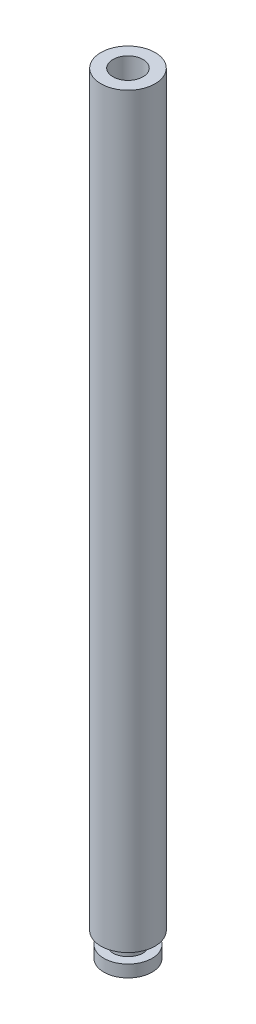
SolidWorks part; units mm, degrees
ref_plane "Front Plane" through (0, 0, 0) normal (0, 0, 1) x (1, 0, 0)
ref_plane "Top Plane" through (0, 0, 0) normal (0, 1, 0) x (1, 0, 0)
ref_plane "Right Plane" through (0, 0, 0) normal (1, 0, 0) x (0, 0, -1)
sketch "Sketch1" plane through (0, 0, 0) normal (0, 1, 0) x (1, 0, 0)
  circle A0 centre (-0.522, 0.5111) radius 1
  circle A1 centre (-0.522, 0.5111) radius 2.25
  dimension "D1" = 2
  dimension "D2" = 4.5
extrude "Boss-Extrude1" add sketch "Sketch1" along normal blind 62 contours A1
extrude "Boss-Extrude2" add sketch "Sketch1<3>" along normal blind 1 contours A0 region at (-0.522, 0, -0.5111)
sketch "Sketch1<3>" plane through (0, 0, 0) normal (0, 1, 0) x (1, 0, 0) same geometry as "Sketch1"
sketch "Sketch5" plane through (0, 0, 0) normal (0, -1, 0) x (1, 0, 0)
  circle A3 centre (-0.522, -0.5111) radius 1.25
  dimension "D1" = 2.5
extrude "Boss-Extrude3" add sketch "Sketch5" along normal blind 1 contours A3
sketch "Sketch6" plane through (0, -1, 0) normal (0, -1, 0) x (1, 0, 0)
  circle A0 centre (-0.522, -0.5111) radius 2
  dimension "D1" = 4
extrude "Boss-Extrude4" add sketch "Sketch6" along normal blind 1
sketch "Sketch8" plane through (0, -2, 0) normal (0, -1, 0) x (-1, 0, 0)
  circle A0 centre (0.522, 0.5111) radius 1.5
  dimension "D1" = 3
sketch "Sketch11" plane through (0, 62, 0) normal (0, 1, 0) x (1, 0, 0)
  text T0 "VIII" font "Century Gothic" height in points 5
sketch "Sketch12" plane through (0, 62, 0) normal (0, 1, 0) x (1, 0, 0)
  circle A0 centre (-0.522, 0.5111) radius 1.25
extrude "Cut-Extrude1" cut sketch "Sketch12" against normal blind 5
